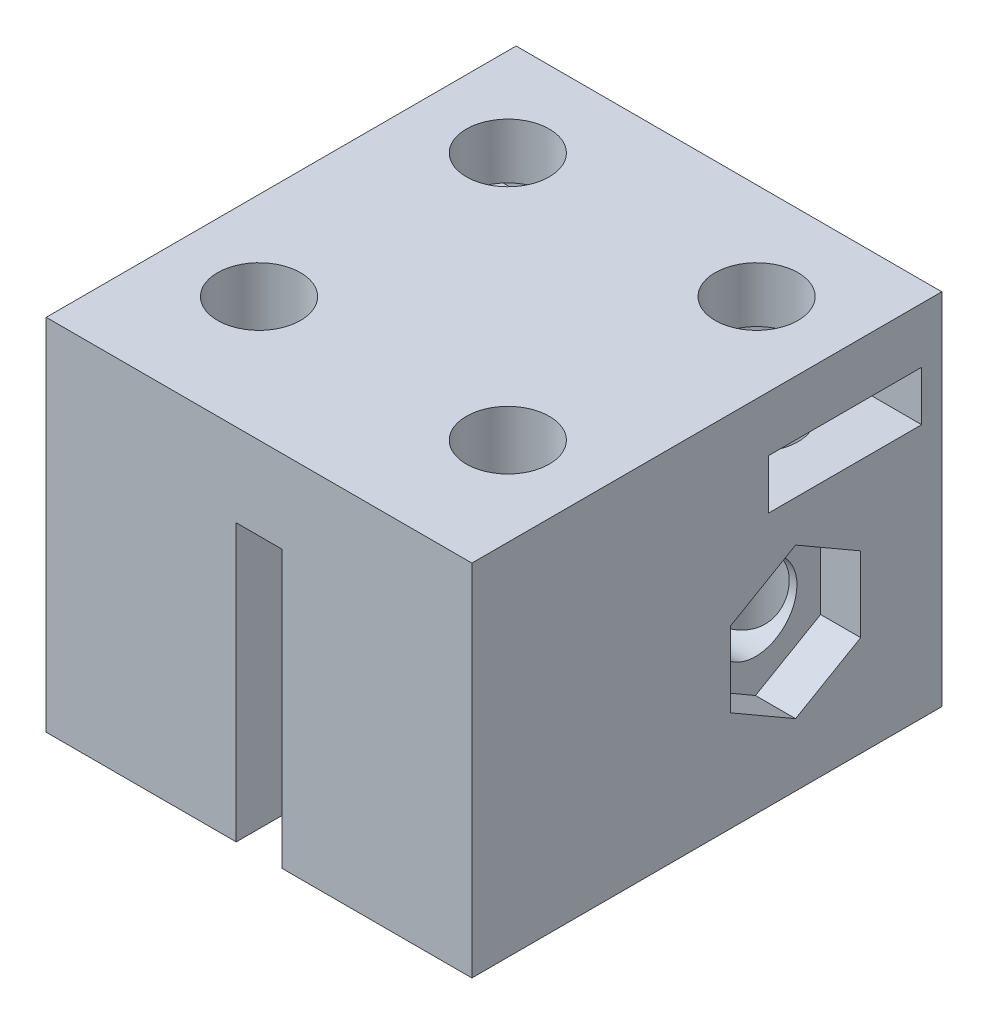
SolidWorks part; units mm, degrees
ref_plane "Front Plane" through (0, 0, 0) normal (0, 0, 1) x (1, 0, 0)
ref_plane "Top Plane" through (0, 0, 0) normal (0, 1, 0) x (1, 0, 0)
ref_plane "Right Plane" through (0, 0, 0) normal (1, 0, 0) x (0, 0, -1)
sketch "Sketch2" plane through (0, 0, 0) normal (0, 0, 1) x (1, 0, 0)
  line L0 (7.7, 13) -> (7.7, -2) construction
  line L1 (0, 0) -> (6.875, 0)
  line L2 (0, 0) -> (0, 13)
  line L3 (0, 13) -> (15.4, 13)
  line L4 (15.4, 0) -> (15.4, 13)
  line L5 (7.7, 5) -> (15.4, 5) construction
  line L6 (6.875, 10) -> (8.525, 10)
  line L7 (6.875, 10) -> (6.875, 0)
  line L9 (8.525, 10) -> (8.525, 0)
  line L10 (6.875, 10) -> (8.525, 0) construction
  line L11 (6.875, 0) -> (8.525, 10) construction
  line L12 (8.525, 0) -> (15.4, 0)
  point P7 (7.7, 5)
  dimension "D1" = 15.4
  dimension "D2" = 10
  dimension "D3" = 3
  dimension "D4" = 1.65
extrude "Boss-Extrude1" add sketch "Sketch2" against normal blind 17
ref_plane "Plane2" through (0, 11, 0) normal (0, 1, 0) x (1, 0, 0)
sketch "Sketch3" plane through (15.4, 0, 0) normal (1, 0, 0) x (0, 0, -1)
  line L0 (14.065, 3.6303) -> (11.71, 2.2707)
  line L1 (0, 0) -> (0, 13) construction
  line L2 (17, 10) -> (0, 10) construction
  line L3 (11.71, 2.2707) -> (9.355, 3.6303)
  line L4 (9.355, 3.6303) -> (9.355, 6.3497)
  line L5 (9.355, 6.3497) -> (11.71, 7.7093)
  line L6 (11.71, 7.7093) -> (14.065, 6.3497)
  line L7 (14.065, 6.3497) -> (14.065, 3.6303)
  line L8 (9.355, 6.3497) -> (14.065, 3.6303) construction
  line L9 (11.71, 7.7093) -> (11.71, 2.2707) construction
  line L10 (9.355, 3.6303) -> (14.065, 6.3497) construction
  circle A0 centre (11.71, 4.99) radius 1.5
  dimension "D1" = 5.01
  dimension "D3" = 3
  dimension "D2" = 11.71
extrude "Cut-Extrude1" cut sketch "Sketch3" against normal through all contours A0 region at (15.4, 4.99, -11.71)
sketch "Sketch4" plane through (0, 11, 0) normal (0, 1, 0) x (1, 0, 0)
  line L0 (7.7, 0) -> (7.7, 17) construction
  line L1 (15.4, 0) -> (0, 0) construction
  line L2 (15.4, 17) -> (0, 17) construction
  line L3 (7.7, 9) -> (0, 9) construction
  line L4 (3.2, 4.5) -> (12.2, 4.5) construction
  line L5 (3.2, 4.5) -> (3.2, 13.5) construction
  line L6 (3.2, 13.5) -> (12.2, 13.5) construction
  line L7 (12.2, 4.5) -> (12.2, 13.5) construction
  line L8 (3.2, 4.5) -> (12.2, 13.5) construction
  line L9 (3.2, 13.5) -> (12.2, 4.5) construction
  line L10 (9.8, 12.1144) -> (9.8, 14.8856)
  line L11 (3.2, 16.2713) -> (0.8, 14.8856)
  line L12 (0.8, 14.8856) -> (0.8, 12.1144)
  line L13 (0.8, 12.1144) -> (3.2, 10.7287)
  line L14 (3.2, 10.7287) -> (5.6, 12.1144)
  line L15 (5.6, 12.1144) -> (5.6, 14.8856)
  line L16 (5.6, 14.8856) -> (3.2, 16.2713)
  line L17 (12.2, 10.7287) -> (9.8, 12.1144)
  line L18 (14.6, 12.1144) -> (12.2, 10.7287)
  line L19 (14.6, 14.8856) -> (14.6, 12.1144)
  line L20 (12.2, 16.2713) -> (14.6, 14.8856)
  line L21 (9.8, 14.8856) -> (12.2, 16.2713)
  line L22 (4.5597, 6.855) -> (5.9193, 4.5) construction
  line L23 (1.8403, 6.855) -> (4.5597, 6.855) construction
  line L24 (0.4807, 4.5) -> (1.8403, 6.855) construction
  line L25 (1.8403, 2.145) -> (0.4807, 4.5) construction
  line L26 (5.9193, 4.5) -> (4.5597, 2.145) construction
  line L27 (10.8403, 6.855) -> (9.4807, 4.5) construction
  line L28 (13.5597, 6.855) -> (10.8403, 6.855) construction
  line L29 (14.9193, 4.5) -> (13.5597, 6.855) construction
  line L30 (13.5597, 2.145) -> (14.9193, 4.5) construction
  line L31 (9.4807, 4.5) -> (10.8403, 2.145) construction
  line L32 (10.8403, 2.145) -> (13.5597, 2.145) construction
  line L33 (4.5597, 2.145) -> (1.8403, 2.145) construction
  line L45 (12.2, 13.5) -> (15.4, 13.5) construction
  line L46 (15.4, 17) -> (15.4, 0) construction
  line L47 (3.2, 13.5) -> (0, 13.5) construction
  line L48 (0, 17) -> (0, 0) construction
  circle A0 centre (3.2, 13.5) radius 1.5
  circle A1 centre (3.2, 4.5) radius 1.5
  circle A2 centre (3.2, 13.5) radius 2.4 construction
  circle A3 centre (12.2, 4.5) radius 1.5
  circle A4 centre (12.2, 13.5) radius 1.5
  point P7 (7.7, 9)
  dimension "D4" = 3
  dimension "D5" = 4.8
  dimension "D1" = 9
  dimension "D2" = 9
  dimension "D3" = 9
extrude "Cut-Extrude3" cut sketch "Sketch4<3>" against normal blind 1.8
sketch "Sketch4<3>" plane through (0, 11, 0) normal (0, 1, 0) x (1, 0, 0) same geometry as "Sketch4"
extrude "Cut-Extrude2" cut sketch "Sketch4" against normal through all and the other way through all contours A0 | A4 | A1 | A3 region at (3.2, 11, -13.5) region at (3.2, 11, -4.5) region at (12.2, 11, -4.5) region at (12.2, 11, -13.5)
extrude "Cut-Extrude4" cut sketch "Sketch3<3>" against normal blind 1.45
sketch "Sketch3<3>" plane through (15.4, 0, 0) normal (1, 0, 0) x (0, 0, -1) same geometry as "Sketch3"
ref_plane "Plane1" through (7.7, 0, 0) normal (1, 0, 0) x (0, 0, -1)
mirror "Mirror1" about plane through (7.7, 0, 0) normal (1, 0, 0) of "Cut-Extrude4"
sketch "Sketch5" plane through (0, 0, 0) normal (0, 0, 1) x (1, 0, 0)
  line L0 (7.7, 10) -> (7.7, 13)
  line L1 (6.875, 10) -> (8.525, 10) construction
  line L2 (15.4, 13) -> (0, 13) construction
sketch "Sketch6" plane through (0, 0, 0) normal (-1, 0, 0) x (0, 0, 1)
  line L0 (-16.2713, 11) -> (-10.7287, 11)
  line L1 (-10.7287, 11) -> (-10.7287, 9.2)
  line L2 (-10.7287, 9.2) -> (-16.2713, 9.2)
  line L3 (-16.2713, 9.2) -> (-16.2713, 11)
  point P0 (-16.2713, 11)
  point P2 (-10.7287, 11)
  dimension "D1" = 1.8
extrude "Cut-Extrude5" cut sketch "Sketch6" against normal up to vertex (3.2 mm away) up to point (3.2, 11, -10.7287)
sketch "Sketch7" plane through (5.6, 0, 0) normal (-1, 0, 0) x (0, 0, 1)
  line L0 (-12.1144, 9.2) -> (-12.1144, 11) construction
  line L1 (-14.8856, 11) -> (-12.1144, 11)
  line L2 (-14.8856, 11) -> (-14.8856, 9.2)
  line L3 (-14.8856, 9.2) -> (-12.1144, 9.2)
  line L4 (-12.1144, 11) -> (-12.1144, 9.2)
  line L5 (-12.1144, 9.2) -> (-14.8856, 9.2) construction
  line L6 (-12.1144, 11) -> (-14.8856, 11) construction
  line L7 (-14.8856, 9.2) -> (-14.8856, 11) construction
extrude "Cut-Extrude6" cut sketch "Sketch7" against normal through all
mirror "Mirror2" about plane through (7.7, 0, 0) normal (1, 0, 0) of "Cut-Extrude5"
